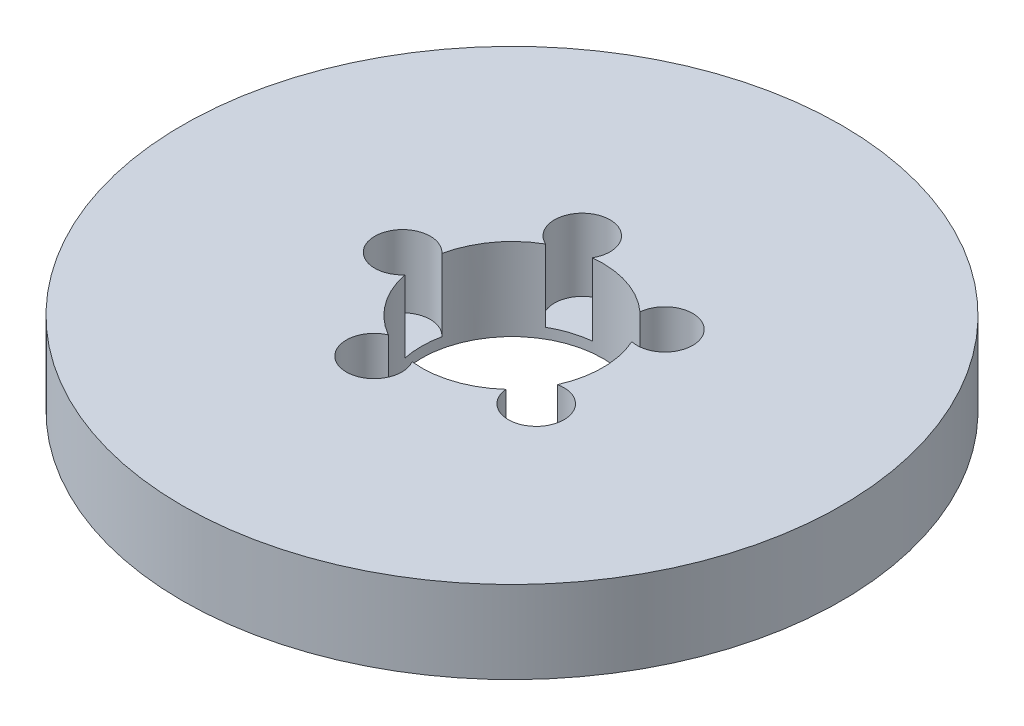
SolidWorks part; units mm, degrees
ref_plane "Front Plane" through (0, 0, 0) normal (0, 0, 1) x (1, 0, 0)
ref_plane "Top Plane" through (0, 0, 0) normal (0, 1, 0) x (1, 0, 0)
ref_plane "Right Plane" through (0, 0, 0) normal (1, 0, 0) x (0, 0, -1)
sketch "Sketch1" plane through (0, 0, 0) normal (0, 1, 0) x (1, 0, 0)
  circle A0 centre (0, 0) radius 100
  dimension "FLANGE_OD" = 200
extrude "Boss-Extrude1" add sketch "Sketch1" along normal blind 25
sketch "Sketch2" plane through (0, 0, 0) normal (0, 1, 0) x (1, 0, 0)
  circle A0 centre (0, 0) radius 27.5
  dimension "BORE_D" = 55
extrude "Cut-Extrude1" cut sketch "Sketch2" along normal through all
sketch "Sketch3" plane through (0, 25, 0) normal (0, 1, 0) x (1, 0, 0)
  circle A0 centre (0, 0) radius 33.2106 construction
  circle A1 centre (-33.2106, 0) radius 8.4304
  dimension "BOLT_D" = 16.8608
  dimension "BOLT_PCD" = 66.4211
extrude "Cut-Extrude2" cut sketch "Sketch3" against normal blind 21.8752
pattern_circular "CirPattern1" count 5 over 360 about axis through (0, 0, 0) along (0, 1, 0) of "Cut-Extrude2"
